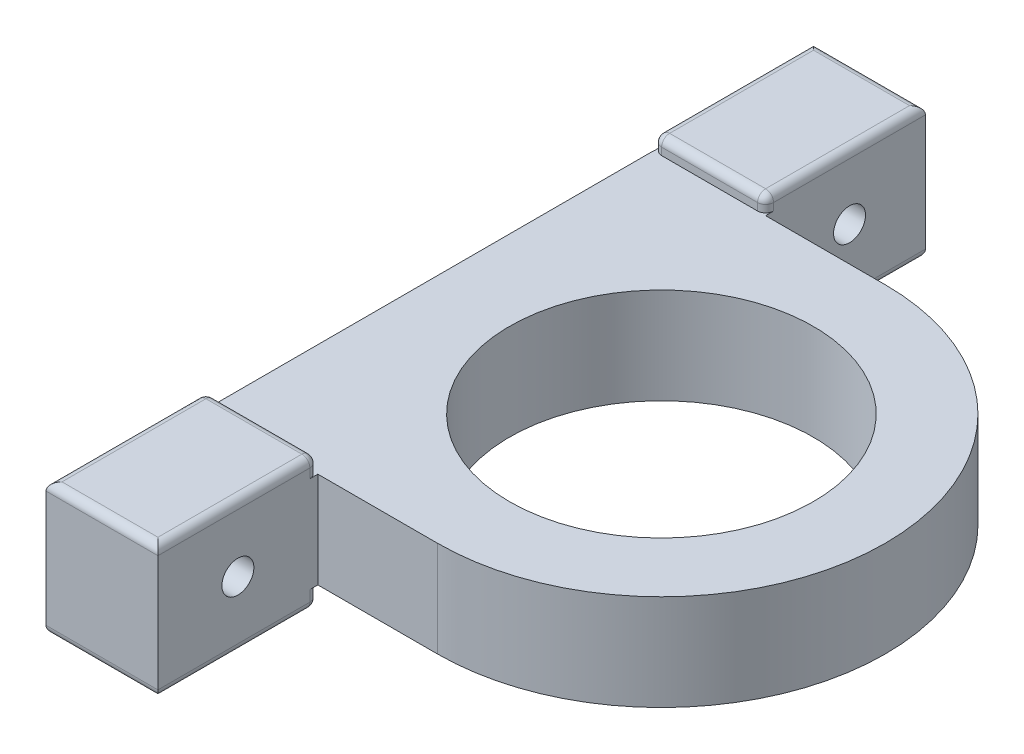
SolidWorks part; units mm, degrees
ref_plane "Front Plane" through (0, 0, 0) normal (0, 0, 1) x (1, 0, 0)
ref_plane "Top Plane" through (0, 0, 0) normal (0, 1, 0) x (1, 0, 0)
ref_plane "Right Plane" through (0, 0, 0) normal (1, 0, 0) x (0, 0, -1)
sketch "Sketch1" plane through (0, 0, 0) normal (0, 1, 0) x (1, 0, 0)
  line L1 (0, -14) -> (-14.5, -14)
  line L2 (0, 14) -> (-14.5, 14)
  line L4 (-14.5, -14) -> (-14.5, 14)
  circle A0 centre (0, 0) radius 9.5
  arc A1 (0, -14) -> (0, 14) centre (0, 0) ccw
extrude "Boss-Extrude1" add sketch "Sketch1" along normal blind 6
sketch "Sketch4" plane through (0, 0, -14) normal (0, 0, -1) x (-1, 0, 0)
  line L10 (14.4846, 6.959) -> (7.8168, 6.959)
  line L11 (14.4846, 6.959) -> (14.4846, -1.308)
  line L12 (14.4846, -1.308) -> (7.8168, -1.308)
  line L13 (7.8168, 6.959) -> (7.8168, -1.308)
extrude "Boss-Extrude2" add sketch "Sketch4" along normal blind 10
sketch "Sketch6" plane through (-14.4846, 0, 0) normal (-1, 0, 0) x (0, 0, 1)
  line L1 (-24, 6.959) -> (-14, 6.959)
  line L2 (-24, 6.959) -> (-24, -1.308)
  line L3 (-24, -1.308) -> (-14, -1.308)
  line L4 (-14, 6.959) -> (-14, -1.308)
  line L5 (14, 7.0836) -> (14, -1.1835)
  line L6 (24, -1.1835) -> (14, -1.1835)
  line L7 (24, 7.0836) -> (24, -1.1835)
  line L8 (24, 7.0836) -> (14, 7.0836)
extrude "Boss-Extrude3" add sketch "Sketch6" against normal blind 7
fillet "Fillet7" radius 0.5 4 edges at (-10.9846, -1.1835, 24) (-7.4846, -1.1835, 19) (-10.9846, -1.1835, 14) (-14.4846, -1.1835, 19)
fillet "Fillet9" radius 0.5 5 edges at (-7.4846, 6.5418, 14) (-10.9846, 7.0836, 14) (-14.4846, 6.5418, 14) (-7.631, -1.037, 14.1464) (-7.4846, -0.3417, 14)
fillet "Fillet10" radius 0.5 9 edges at (-14.3381, 6.9371, 14.1464) (-7.631, 6.9371, 14.1464) (-10.9846, 7.0836, 24) (-14.4846, 7.0836, 19.25) (-7.4846, 7.0836, 19.25) (-7.4846, -1.308, -19) (-10.9846, -1.308, -24) (-14.4846, -1.308, -19) (-10.9846, -1.308, -14)
fillet "Fillet12" radius 0.5 5 edges at (-7.631, -1.1616, -14.1464) (-7.4846, -0.404, -14) (-7.4846, 6.4795, -14) (-14.4846, 6.4795, -14) (-10.9846, 6.959, -14)
fillet "Fillet13" radius 0.5 5 edges at (-7.631, 6.8125, -14.1464) (-14.3381, 6.8125, -14.1464) (-10.9846, 6.959, -24) (-7.4846, 6.959, -19.25) (-14.4846, 6.959, -19.25)
sketch "Sketch7" plane through (-14.4846, 0, 0) normal (-1, 0, 0) x (0, 0, 1)
  circle A0 centre (-19.25, 2.9083) radius 1
extrude "Cut-Extrude1" cut sketch "Sketch7" against normal blind 8
sketch "Sketch8" plane through (-14.4846, 0, 0) normal (-1, 0, 0) x (0, 0, 1)
  circle A0 centre (19, 2.95) radius 1
extrude "Cut-Extrude2" cut sketch "Sketch8" against normal blind 8
